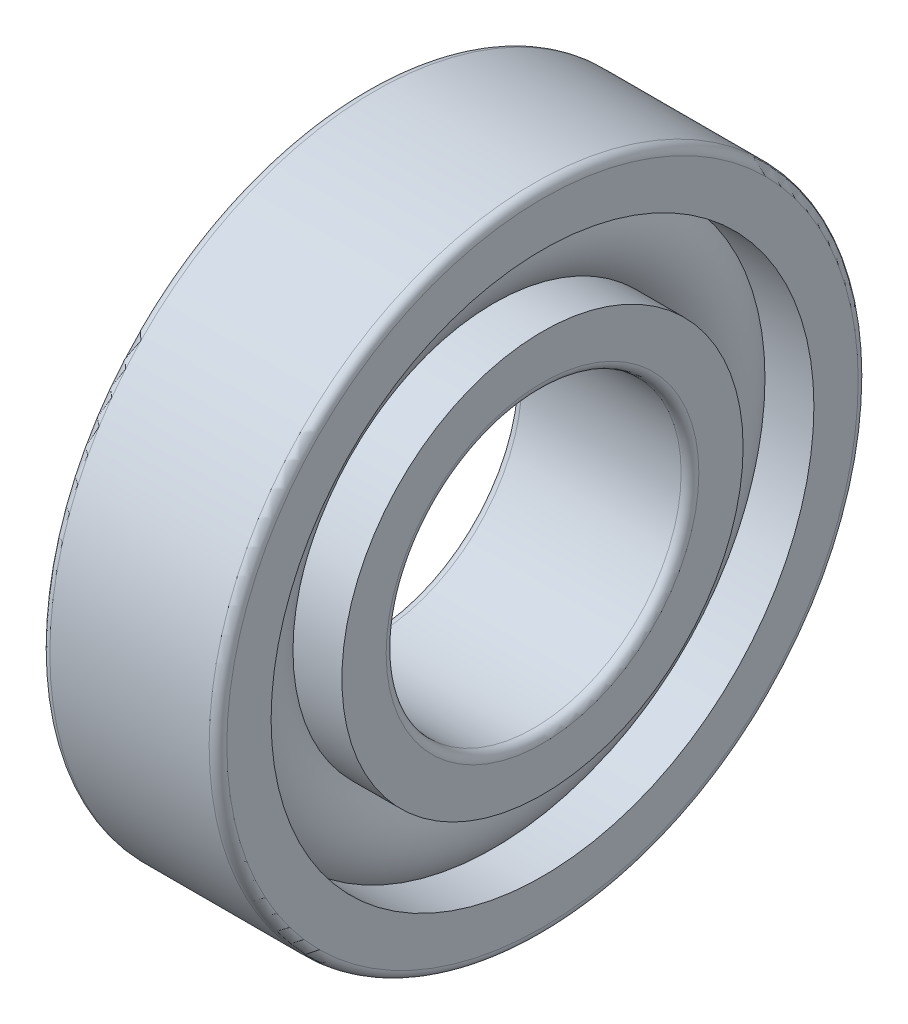
SolidWorks part; units mm, degrees
ref_plane "Plane1" through (0, 0, 0) normal (0, 0, 1) x (1, 0, 0)
ref_plane "Plane2" through (0, 0, 0) normal (0, 1, 0) x (1, 0, 0)
ref_plane "Plane3" through (0, 0, 0) normal (1, 0, 0) x (0, 0, -1)
sketch "Clipboard" plane through (0, 0, 0) normal (0, 0, 1) x (1, 0, 0)
  line L0 (-10, 0) -> (10, 0) construction
  line L1 (0, 0) -> (22.3471, -0.7804)
  line L2 (0, 0) -> (3.9976, 0.1396)
  line L3 (0, 0) -> (22.3471, -0.7804)
  line L4 (0, 0) -> (-22.3573, -0.3902)
  dimension "BallCLRad" = 4
sketch "CagSpiSke" plane through (0, 0, 0) normal (0, 0, 1) x (1, 0, 0)
  line L0 (0.09, 3.85) -> (0.09, 4.15)
  line L1 (0.09, 4.15) -> (-0.09, 4.15)
  line L2 (-0.09, 4.15) -> (-0.09, 3.85)
  line L3 (-0.09, 3.85) -> (0.09, 3.85)
  line L4 (-20.6375, 0) -> (20.6375, 0) construction
  line L5 (0, 0) -> (0, 23.7692) construction
  dimension "OD" = 8.3
  dimension "ID" = 7.7
revolve "CageSpine" add sketch "CagSpiSke" angle 0.001 about L4 reverse direction yes
ref_axis "Axis1" through (-50, 0, 0) along (1, 0, 0)
sketch "CagBalSke" plane through (0, 0, 0) normal (0, 0, 1) x (1, 0, 0)
  line L0 (-0.99, 4) -> (0.99, 4)
  line L1 (-1.905, 4) -> (1.905, 4) construction
  line L2 (-10, 0) -> (10, 0) construction
  line L3 (0, 0) -> (0, 24) construction
  arc A0 (0.99, 4) -> (-0.99, 4) centre (0, 4) cw
  dimension "BallCLRad" = 4
revolve "CageBall" [suppressed] add sketch "CagBalSke" angle 360 about L1 reverse direction yes
pattern_circular "CageBalls" [suppressed] count 2 every 180 about axis through (-50, 0, 0) along (1, 0, 0)
sketch "CagTrmODSke" plane through (0, 0, 0) normal (0, 0, 1) x (1, 0, 0)
  line L0 (0.991, 4.15) -> (0.991, 4.991)
  line L1 (0.991, 4.991) -> (-0.991, 4.991)
  line L2 (-0.991, 4.991) -> (-0.991, 4.15)
  line L3 (-0.991, 4.15) -> (0.991, 4.15)
  line L4 (-20.6375, 0) -> (20.6375, 0) construction
  line L5 (0, 0) -> (0, 25) construction
  dimension "Width" = 1.982
  dimension "ID" = 8.3
  dimension "OD" = 9.982
revolve "CageTrimOD" [suppressed] cut sketch "CagTrmODSke" angle 360 about L4 reverse direction yes
sketch "CagTrmIDSke" plane through (0, 0, 0) normal (0, 0, 1) x (1, 0, 0)
  line L0 (0.991, 3.011) -> (0.991, 3.85)
  line L1 (0.991, 3.85) -> (-0.991, 3.85)
  line L2 (-0.991, 3.85) -> (-0.991, 3.011)
  line L3 (-0.991, 3.011) -> (0.991, 3.011)
  line L4 (-20.6375, 0) -> (20.6375, 0) construction
  line L5 (0, 0) -> (0, 25) construction
  dimension "Width" = 1.982
  dimension "ID" = 6.022
  dimension "OD" = 7.7
revolve "CageTrimID" [suppressed] cut sketch "CagTrmIDSke" angle 360 about L4 reverse direction yes
sketch "BalSimSke" plane through (0, 0, 0) normal (0, 0, 1) x (1, 0, 0)
  line L0 (-10, 0) -> (10, 0) construction
  line L1 (-10, 4) -> (10, 4) construction
  line L2 (0, 0) -> (0, 23) construction
  circle A0 centre (0, 4) radius 0.9
  dimension "BallCLRad" = 4
  dimension "Ball_diameter" = 1.8
revolve "BallsSimplified" add sketch "BalSimSke" angle 360 about L0
sketch "BalDetSke" plane through (0, 0, 0) normal (0, 0, 1) x (1, 0, 0)
  line L0 (-0.9, 4) -> (0.9, 4)
  line L1 (-1.905, 4) -> (1.905, 4) construction
  line L2 (0, 0) -> (0, 25) construction
  arc A0 (0.9, 4) -> (-0.9, 4) centre (0, 4) cw
  dimension "BallCLRad" = 4
  dimension "Ball_diameter" = 1.8
revolve "BallDetailed" [suppressed] add sketch "BalDetSke" angle 360 about L1 reverse direction yes
sketch "InnRacSke" plane through (0, 0, 0) normal (0, 0, 1) x (1, 0, 0)
  line L0 (-0.6369, 3.4) -> (-1.5, 3.4)
  line L1 (-1.5, 3.4) -> (-1.5, 2.65)
  line L2 (-1.35, 2.5) -> (1.35, 2.5)
  line L3 (1.5, 2.65) -> (1.5, 3.4)
  line L4 (1.5, 3.4) -> (0.6369, 3.4)
  line L5 (-20.6375, 0) -> (20.6375, 0) construction
  line L6 (0, 0) -> (0, 30) construction
  arc A0 (-1.5, 2.65) -> (-1.35, 2.5) centre (-1.35, 2.65) ccw
  arc A1 (1.35, 2.5) -> (1.5, 2.65) centre (1.35, 2.65) ccw
  arc A2 (0.6369, 3.4) -> (-0.6369, 3.4) centre (0, 4) cw
  dimension "BallCLRad" = 4
  dimension "Fillet_radius" = 0.15
  dimension "Ball_diameter" = 1.75
  dimension "ID" = 5
  dimension "OD" = 6.8
  dimension "Width" = 3
revolve "InnerRace" add sketch "InnRacSke" angle 360 about L5 reverse direction yes
sketch "OutRacSke" plane through (0, 0, 0) normal (0, 0, 1) x (1, 0, 0)
  line L0 (-0.6369, 4.6) -> (-1.5, 4.6)
  line L1 (-1.5, 4.6) -> (-1.5, 5.35)
  line L2 (-1.35, 5.5) -> (1.35, 5.5)
  line L3 (1.5, 5.35) -> (1.5, 4.6)
  line L4 (1.5, 4.6) -> (0.6369, 4.6)
  line L5 (-20.6375, 0) -> (20.6375, 0) construction
  line L6 (0, 0) -> (0, 30) construction
  arc A0 (-1.5, 5.35) -> (-1.35, 5.5) centre (-1.35, 5.35) cw
  arc A1 (1.35, 5.5) -> (1.5, 5.35) centre (1.35, 5.35) cw
  arc A2 (0.6369, 4.6) -> (-0.6369, 4.6) centre (0, 4) ccw
  dimension "BallCLRad" = 4
  dimension "Fillet_radius" = 0.15
  dimension "Ball_diameter" = 1.75
  dimension "Width" = 3
revolve "OuterRace" add sketch "OutRacSke" angle 360 about L5 reverse direction yes
pattern_circular "BallsDetailed" [suppressed] count 2 every 180 about axis through (-50, 0, 0) along (1, 0, 0)
equation "\"BallCLRad@Clipboard\" = ( \"OD@OutRacSke\" + \"ID@InnRacSke\" ) / 4"
equation "\"BallCLRad@BalSimSke\" = \"BallCLRad@Clipboard\""
equation "\"BallCLRad@BalDetSke\" = \"BallCLRad@Clipboard\""
equation "\"BallCLRad@InnRacSke\" = \"BallCLRad@Clipboard\""
equation "\"BallCLRad@OutRacSke\" = \"BallCLRad@Clipboard\""
equation "\"Ball_diameter@InnRacSke\" = \"Ball_diameter@BalDetSke\" - 0.05"
equation "\"Ball_diameter@OutRacSke\" = \"Ball_diameter@BalDetSke\" - 0.05"
equation "\"Ball_diameter@BalSimSke\" = \"Ball_diameter@BalDetSke\""
equation "\"Width@OutRacSke\" = \"Width@InnRacSke\""
equation "\"Fillet_radius@OutRacSke\" = \"Fillet_radius@InnRacSke\""
equation "\"Max_count@Clipboard\" = int( 3.14159265 / atn(( \"Ball_diameter@BalDetSke\" / 2) / sqr( \"BallCLRad@Clipboard\"  *  \"BallCLRad@Clipboard\" - ( \"Ball_diameter@BalDetSke\" / 2) *  ( \"Ball_diameter@BalDetSke\" / 2))))"
equation "\"Max_count@Clipboard\" = ((sgn( \"Max_count@Clipboard\" - \"Count@Clipboard\" )-1)*( \"Max_count@Clipboard\" - \"Count@Clipboard\" ))/-2+ \"Count@Clipboard\""
equation "\"Count@BallsDetailed\" = int( \"Show_count@Clipboard\" ) "
equation "\"Count@BallsDetailed\" = ((sgn( \"Count@BallsDetailed\" - \"Max_count@Clipboard\" )-1)*( \"Count@BallsDetailed\" - \"Max_count@Clipboard\" ))/-2+ \"Max_count@Clipboard\""
equation "\"Count@BallsDetailed\" = ((sgn( \"Count@BallsDetailed\" - \"Min_count@Clipboard\" )+1)*( \"Count@BallsDetailed\" - \"Min_count@Clipboard\"))/2 +\"Min_count@Clipboard\""
equation "\"Angle@BallsDetailed\" = 360.0 / \"Max_count@Clipboard\""
equation "\"BallCLRad@CagBalSke\" = \"BallCLRad@Clipboard\""
equation "\"Count@CageBalls\" = \"Count@BallsDetailed\""
equation "\"Angle@CageBalls\" = \"Angle@BallsDetailed\""
equation "\"Angle@CageSpine\" =  \"Angle@CageBalls\" * ( \"Count@CageBalls\" -1 + int( \"Count@CageBalls\" / \"Max_count@Clipboard\" ) )  + 0.001 -  int( \"Count@CageBalls\" / \"Max_count@Clipboard\" ) * 0.001"
equation "\"Angle@CageSpine\" =  \"Angle@CageSpine\" * int( \"Min_count@Clipboard\" / 2) + int(1 / \"Min_count@Clipboard\")  * 0.001"
equation "\"CageWallOD@CagBalSke\" =  \"Ball_diameter@BalDetSke\" * 1.1"
equation "\"Thickness@CagSpiSke\" =  \"Ball_diameter@BalDetSke\" * 0.1"
equation "\"OD@CagTrmODSke\" = \"BallCLRad@Clipboard\" * 2 + \"CageWallOD@CagBalSke\" + 0.002"
equation "\"ID@CagTrmODSke\" = \"BallCLRad@Clipboard\" * 2 + \"Ball_diameter@BalDetSke\" / 6"
equation "\"OD@CagTrmIDSke\" = \"BallCLRad@Clipboard\" * 2 - \"Ball_diameter@BalDetSke\" / 6"
equation "\"ID@CagTrmIDSke\" = \"BallCLRad@Clipboard\" * 2 - \"CageWallOD@CagBalSke\" + 0.002"
equation "\"OD@CagSpiSke\" = \"ID@CagTrmODSke\""
equation "\"ID@CagSpiSke\" = \"OD@CagTrmIDSke\""
equation "\"Width@CagTrmODSke\" = \"CageWallOD@CagBalSke\" + 0.002"
equation "\"Width@CagTrmIDSke\" = \"CageWallOD@CagBalSke\" + 0.002"
